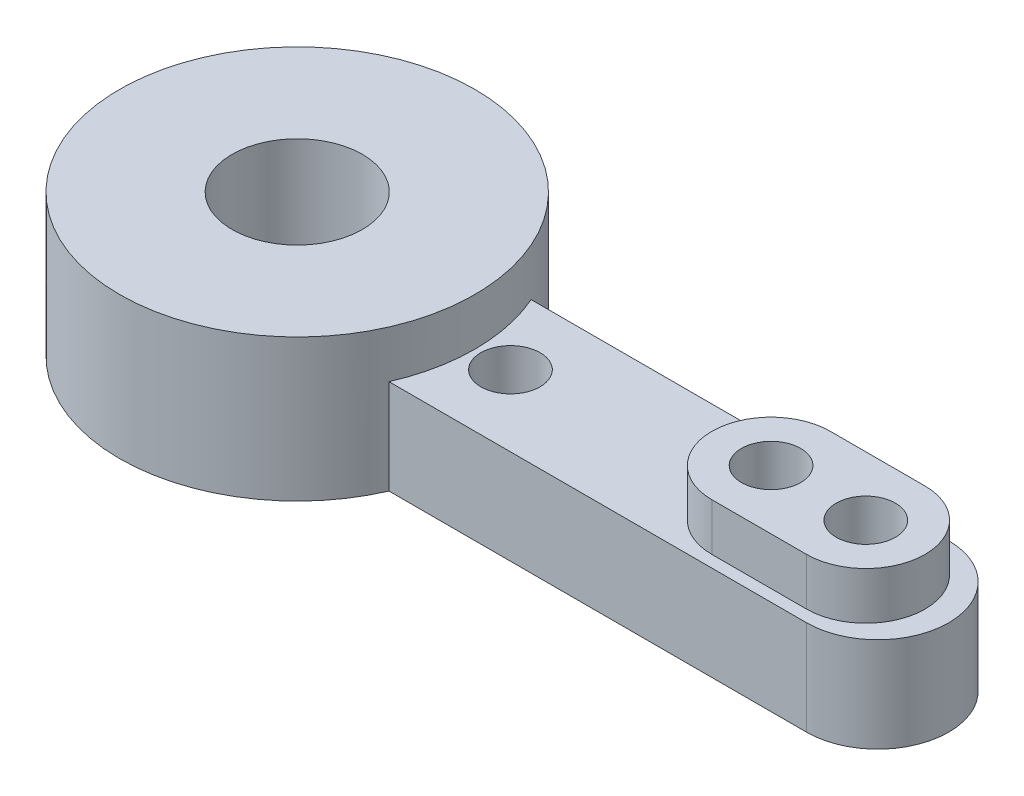
SolidWorks part; units mm, degrees
note: The reader was unsure of these and kept them because the rebuilt part matched: shared geometry of "草图1<3>".
ref_plane "前视基准面" through (0, 0, 0) normal (0, 0, 1) x (1, 0, 0)
ref_plane "上视基准面" through (0, 0, 0) normal (0, 1, 0) x (1, 0, 0)
ref_plane "右视基准面" through (0, 0, 0) normal (1, 0, 0) x (0, 0, -1)
other "Configuration Table"
sketch "草图1" plane through (0, 0, 0) normal (0, 1, 0) x (1, 0, 0)
  line L0 (0, 0) -> (24.5, 0) construction
  line L1 (0, 3) -> (24.5, 3)
  line L2 (0, -3) -> (24.5, -3)
  circle A0 centre (0, 0) radius 7.5
  arc A1 (0, 3) -> (0, -3) centre (0, 0) ccw
  arc A2 (24.5, -3) -> (24.5, 3) centre (24.5, 0) ccw
  point P4 (12.25, 0)
  point P9 (24, 0)
  point P10 (20, 0)
  point P11 (9, 0)
  point P14 (11.9137, -29.7375)
  point P15 (13.9045, -4.7095)
  dimension "D1" = 15
  dimension "D2" = 3
  dimension "D3" = 24.5
  dimension "D4" = 9
  dimension "D5" = 24
  dimension "D6" = 20
extrude "凸台-拉伸1" add sketch "草图1" along normal blind 4
extrude "凸台-拉伸2" add sketch "草图1<3>" along normal blind 6
sketch "草图1<3>" plane through (0, 0, 0) normal (0, 1, 0) x (1, 0, 0) same geometry as "草图1"
sketch "草图2" plane through (0, 4, 0) normal (0, 1, 0) x (1, 0, 0)
  line L0 (0, 0) -> (24.5, 0) construction
  line L1 (20, 0) -> (24, 0) construction
  line L2 (24.5, 3) -> (0, 3)
  line L3 (0, -3) -> (24.5, -3)
  line L4 (24.5, 3) -> (0, 3)
  line L5 (0, -3) -> (24.5, -3)
  line L6 (20, 2.5) -> (24, 2.5)
  line L7 (20, -2.5) -> (24, -2.5)
  arc A0 (20, 2.5) -> (20, -2.5) centre (20, 0) ccw
  circle A1 centre (0, 0) radius 7.5
  circle A2 centre (0, 0) radius 7.5
  arc A3 (24, -2.5) -> (24, 2.5) centre (24, 0) ccw
  arc A4 (24.5, -3) -> (24.5, 3) centre (24.5, 0) ccw
  arc A5 (0, 3) -> (0, -3) centre (0, 0) ccw
  arc A6 (24.5, -3) -> (24.5, 3) centre (24.5, 0) ccw
  arc A7 (0, 3) -> (0, -3) centre (0, 0) ccw
  point P5 (20, 0)
  point P10 (24, 0)
  point P13 (22, 0)
  dimension "D5" = 2.5
  dimension "D3" = 24
  dimension "D4" = 20
  dimension "D1" = 0
  dimension "D2" = 0
extrude "凸台-拉伸3" add sketch "草图2" along normal up to surface (2 mm away) contours L7 A3 L6 A0
sketch "草图3" plane through (0, 0, 0) normal (0, 1, 0) x (1, 0, 0)
  line L0 (20, -2.5) -> (24, -2.5) construction
  line L1 (20, 2.5) -> (24, 2.5) construction
  line L2 (6.8739, 3) -> (24.5, 3) construction
  line L3 (6.8739, -3) -> (24.5, -3) construction
  line L4 (20, -2.5) -> (24, -2.5)
  line L5 (20, 2.5) -> (24, 2.5)
  line L6 (6.8739, 3) -> (24.5, 3)
  line L7 (6.8739, -3) -> (24.5, -3)
  line L8 (0, 0) -> (27.5, 0) construction
  arc A0 (20, 2.5) -> (20, -2.5) centre (20, 0) ccw construction
  arc A1 (24, -2.5) -> (24, 2.5) centre (24, 0) ccw construction
  arc A2 (24.5, -3) -> (24.5, 3) centre (24.5, 0) ccw construction
  circle A3 centre (0, 0) radius 7.5 construction
  arc A4 (20, 2.5) -> (20, -2.5) centre (20, 0) ccw
  arc A5 (24, -2.5) -> (24, 2.5) centre (24, 0) ccw
  arc A6 (24.5, -3) -> (24.5, 3) centre (24.5, 0) ccw
  circle A7 centre (0, 0) radius 7.5
  point P0 (20, 0)
  point P3 (24, 0)
  point P5 (6.8739, 3)
  point P11 (0, 0)
  point P14 (9, 0)
  point P26 (0, 0)
  dimension "D1" = 9
hole_wizard "M3 螺纹孔1" positions "草图3" profile "草图4" tap size "M3" standard "GB"
sketch "草图4" plane through (20, 0, 0) normal (1, 0, 0) x (0, 0, -1)
  line L0 (0, 0) -> (0, 6)
  line L1 (0, 6) -> (1.25, 6)
  line L2 (1.25, 6) -> (1.25, 0)
  line L5 (1.25, 0) -> (0, 0)
  line L11 (0, -6.35) -> (0, 107.95) construction
  dimension "通孔螺纹孔钻头直径" = 2.5
  dimension "通孔螺纹孔钻头深度" = 6
sketch "草图5" plane through (0, 6, 0) normal (0, 1, 0) x (1, 0, 0)
  circle A0 centre (0, 0) radius 2.75
  dimension "D1" = 5.5
extrude "切除-拉伸1" cut sketch "草图5" against normal blind 4 and the other way through all
sketch "草图6" plane through (0, 0, 0) normal (0, -1, 0) x (1, 0, 0)
  circle A0 centre (0, 0) radius 4
  dimension "D1" = 8
extrude "切除-拉伸2" cut sketch "草图6" against normal blind 0.75
